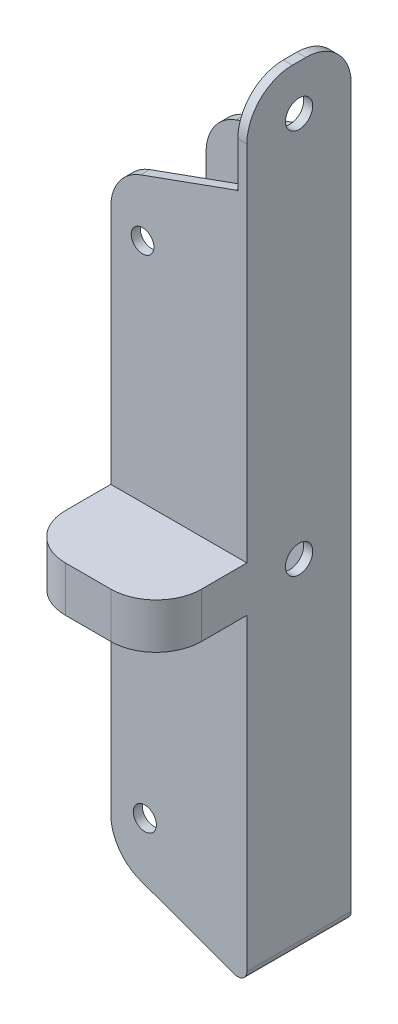
SolidWorks part; units mm, degrees
ref_plane "Front Plane" through (0, 0, 0) normal (0, 0, 1) x (1, 0, 0)
ref_plane "Top Plane" through (0, 0, 0) normal (0, 1, 0) x (1, 0, 0)
ref_plane "Right Plane" through (0, 0, 0) normal (1, 0, 0) x (0, 0, -1)
sketch "Sketch1" plane through (0, 0, 0) normal (0, 0, 1) x (1, 0, 0)
  line L1 (0, 0) -> (30, 0)
  line L2 (0, 0) -> (0, 150)
  line L3 (0, 150) -> (30, 150)
  line L4 (30, 0) -> (30, 150)
  dimension "D1" = 150
  dimension "D2" = 30
extrude "Boss-Extrude2" add sketch "Sketch1" along normal blind 23
sketch "Sketch3" plane through (0, 150, 0) normal (0, 1, 0) x (1, 0, 0)
  line L0 (0, 0) -> (0, -2)
  line L1 (0, 0) -> (30, 0)
  line L2 (0, 0) -> (0, -23)
  line L3 (0, -23) -> (30, -23)
  line L4 (30, 0) -> (30, -23)
  line L5 (0, -23) -> (0, -21)
  line L6 (0, -2) -> (28, -2)
  line L7 (28, -2) -> (28, -21)
  line L10 (0, -2) -> (28, -2)
  line L11 (0, -2) -> (0, -21)
  line L12 (0, -21) -> (28, -21)
  line L13 (28, -2) -> (28, -21)
  line M6 (0, 0) -> (0, -23)
  dimension "D1" = 23
  dimension "D2" = 2
  dimension "D3" = 2
  dimension "D4" = 2
extrude "Cut-Extrude1" cut sketch "Sketch3" against normal blind 193 contours L12 L7 L6 M6 region at (14, 150, 11.5)
sketch "Sketch7" plane through (0, 150, 0) normal (0, 1, 0) x (1, 0, 0)
  line L0 (30, -23) -> (0, -23) construction
  line L1 (30, 0) -> (28.0053, 0)
  line L2 (30, 0) -> (30, -23)
  line L3 (30, -23) -> (28.0053, -23)
  line L4 (28.0053, 0) -> (28.0053, -23)
extrude "Boss-Extrude4" add sketch "Sketch7" along normal blind 20 contours L2 L1 L4 L3
sketch "Sketch8" plane through (30, 0, 0) normal (1, 0, 0) x (0, 0, -1)
  line L0 (-11.5, 0) -> (-11.5, 150)
  line L1 (-23, 0) -> (0, 0) construction
  line L2 (0, 0) -> (0, 170) construction
  line L3 (0, 150) -> (-23, 150)
  line L4 (0, 150) -> (0, 170)
  line L5 (0, 170) -> (-23, 170)
  line L6 (-23, 150) -> (-23, 170)
  line L7 (0, 150) -> (-23, 170)
  line L8 (-23, 150) -> (0, 170)
  circle A0 centre (-11.5, 160) radius 3
  circle A1 centre (-11.5, 75) radius 3
  dimension "D3" = 6
  dimension "D4" = 6
  dimension "D1" = 150
  dimension "D2" = 20
extrude "Cut-Extrude2" cut sketch "Sketch8" against normal blind 20 contours L0 A1 | L0 A1 | L8 A0 L7 | L7 A0 L8 | L8 A0 L7 | L7 A0 L8 region at (30, 75, 12.7732) region at (30, 75, 10.2268) region at (30, 158.2349, 11.5) region at (30, 160, 9.6664) region at (30, 160, 13.3336) region at (30, 161.7651, 11.5)
sketch "Sketch9" plane through (0, 0, 23) normal (0, 0, 1) x (1, 0, 0)
  line L0 (30, 0) -> (30, 170) construction
  line L1 (0, 150) -> (30, 150)
  line L2 (0, 150) -> (0, 80)
  line L3 (0, 80) -> (30, 80)
  line L4 (30, 150) -> (30, 80)
  line L6 (0, 0) -> (30, 0)
  line L7 (0, 0) -> (0, 70)
  line L8 (0, 70) -> (30, 70)
  line L9 (30, 0) -> (30, 70)
  line L10 (0, 80) -> (30, 80)
  line L11 (0, 80) -> (0, 70)
  line L12 (0, 70) -> (30, 70)
  line L13 (30, 80) -> (30, 70)
  line M7 (0, 150) -> (0, 0)
  line M9 (30, 0) -> (30, 170)
  dimension "D1" = 70
  dimension "D2" = 70
  dimension "D3" = 30
extrude "Boss-Extrude5" add sketch "Sketch9" along normal blind 20 contours L8 L3 M7 M9 region at (15, 75, 23)
sketch "Sketch11" plane through (0, 0, 23) normal (0, 0, 1) x (1, 0, 0)
  line L0 (0, 150) -> (14.0027, 150)
  line L1 (28.0053, 150) -> (0, 150) construction
  line L2 (7.0013, 150) -> (7.0013, 130)
  line L3 (0, 0) -> (15, 0)
  line L4 (0, 0) -> (30, 0) construction
  line L5 (7.5, 0) -> (7.5, 20)
  circle A0 centre (7.0013, 130) radius 2.5
  circle A1 centre (7.5, 20) radius 2.5
  dimension "D3" = 5
  dimension "D4" = 5
  dimension "D1" = 20
  dimension "D2" = 20
extrude "Cut-Extrude4" cut sketch "Sketch11" against normal blind 10 contours A0 | A1 region at (5.2836, 128.2822, 23) region at (9.2178, 18.2822, 23)
sketch "Sketch12" plane through (0, 0, 23) normal (0, 0, 1) x (1, 0, 0)
  line L0 (0, 150) -> (0, 140)
  line L1 (0, 150) -> (0, 80) construction
  line L2 (0, 0) -> (0, 10)
  line L3 (0, 70) -> (0, 0) construction
  line L4 (0, 140) -> (27.6984, 150)
  line L5 (27.6984, 150) -> (0, 150)
  line L6 (30, 0) -> (27.6984, 0)
  line L7 (0, 0) -> (30, 0) construction
  line L8 (27.6984, 0) -> (0, 10)
  line L9 (0, 0) -> (27.6984, 0)
  line M2 (0, 150) -> (0, 80)
  line M7 (28.0053, 150) -> (0, 150)
  dimension "D1" = 10
  dimension "D2" = 10
extrude "Cut-Extrude5" cut sketch "Sketch12" against normal blind 30 contours L4 M2 M7 | L2 L9 L8 region at (9.2328, 146.6667, 23) region at (9.2328, 3.3333, 23)
fillet "Fillet1" radius 10 4 edges at (0, 10, 1) (0, 10, 22) (0, 140, 1) (0, 140, 22)
sketch "Sketch13" plane through (0, 0, 23) normal (0, 0, 1) x (1, 0, 0)
  circle A0 centre (7.5, 20) radius 2.5432
extrude "Cut-Extrude6" cut sketch "Sketch13" against normal blind 30
fillet "Fillet2" radius 10 2 edges at (30, 75, 43) (0, 75, 43)
fillet "Fillet3" radius 10 2 edges at (29.0027, 170, 0) (29.0027, 170, 23)
fillet "Fillet4" radius 2 1 edges at (30, 0, 11.5)
